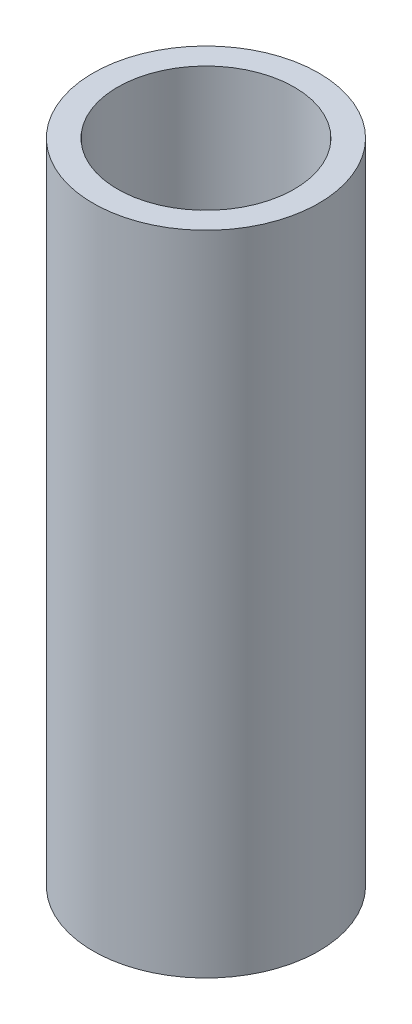
SolidWorks part; units mm, degrees
ref_plane "Front Plane" through (0, 0, 0) normal (0, 0, 1) x (1, 0, 0)
ref_plane "Top Plane" through (0, 0, 0) normal (0, 1, 0) x (1, 0, 0)
ref_plane "Right Plane" through (0, 0, 0) normal (1, 0, 0) x (0, 0, -1)
sketch "Sketch1" plane through (0, 0, 0) normal (0, 1, 0) x (1, 0, 0)
  circle A0 centre (0, 0) radius 30
  dimension "SLEEVE_OD" = 60
extrude "Boss-Extrude1" add sketch "Sketch1" along normal blind 172.1268
sketch "Sketch2" plane through (0, 0, 0) normal (0, 1, 0) x (1, 0, 0)
  circle A0 centre (0, 0) radius 23.4951
  dimension "BORE_D" = 46.9903
extrude "Cut-Extrude1" cut sketch "Sketch2" along normal through all
chamfer "Chamfer1" distance 2.8288 angle 60 rebuild error yes
